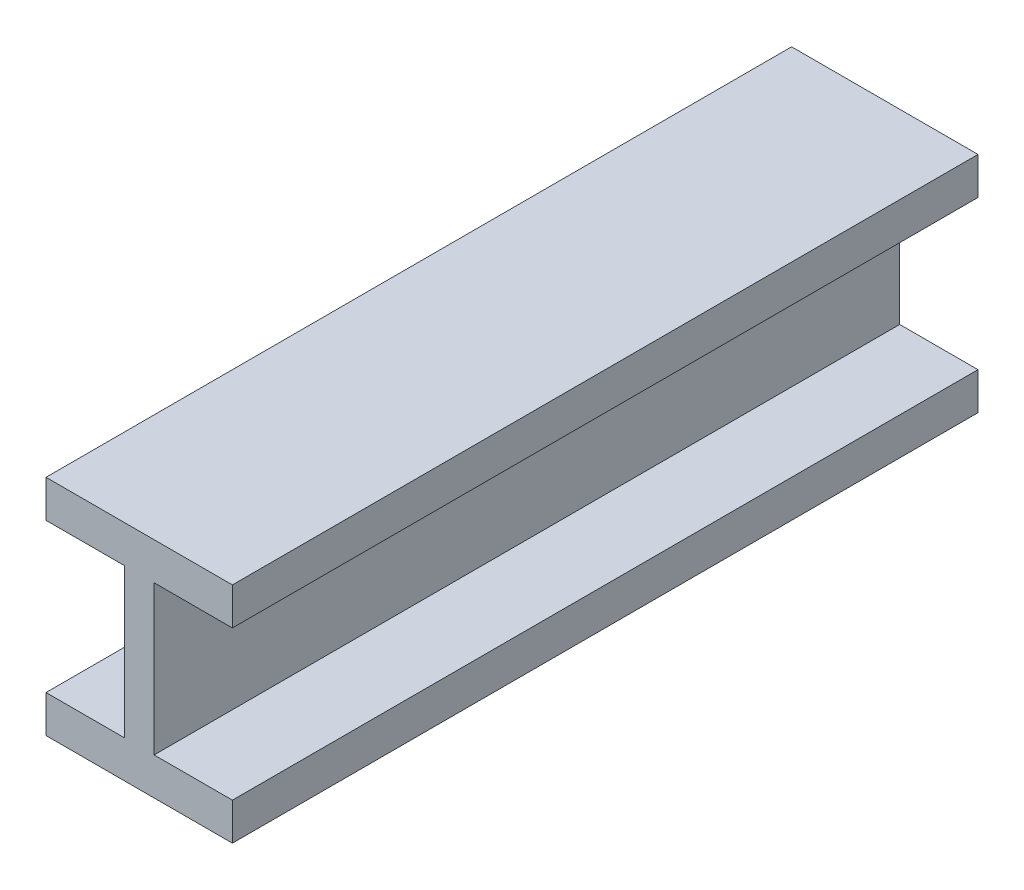
SolidWorks part; units mm, degrees
material "ABS P430"
ref_plane "Front Plane" through (0, 0, 0) normal (0, 0, 1) x (1, 0, 0)
ref_plane "Top Plane" through (0, 0, 0) normal (0, 1, 0) x (1, 0, 0)
ref_plane "Right Plane" through (0, 0, 0) normal (1, 0, 0) x (0, 0, -1)
sketch "Sketch3" plane through (0, 0, 0) normal (0, 1, 0) x (1, 0, 0)
  line L0 (0, 0) -> (0, 100.0652)
  point P3 (0, 50.0326)
  dimension "D1" = 100.0652
sketch "Sketch1" plane through (0, 0, 0) normal (0, 0, 1) x (1, 0, 0)
  line L1 (-12.5, -15) -> (12.5, -15)
  line L2 (-12.5, -15) -> (-12.5, 15)
  line L3 (-12.5, 15) -> (12.5, 15)
  line L4 (12.5, -15) -> (12.5, 15)
  line L5 (-12.5, -15) -> (12.5, 15) construction
  line L6 (-12.5, 15) -> (12.5, -15) construction
  line L7 (-12.5, -10) -> (12.5, -10)
  line L8 (-2, -10) -> (-2, 10)
  line L9 (-12.5, 10) -> (12.5, 10)
  line L10 (2, -10) -> (2, 10)
  line L11 (-2, -10) -> (2, 10) construction
  line L12 (-2, 10) -> (2, -10) construction
  point P0 (0, 0)
  point P6 (0, 0)
  dimension "D1" = 5
  dimension "D2" = 5
  dimension "D3" = 4
  dimension "D4" = 25
  dimension "D5" = 20
extrude "Boss-Extrude1" add sketch "Sketch1" against normal blind 100 contours L2 L9 L4 L3 | L7 L10 L9 L8 | L7 L2 L1 L4 region at (0, -12.5, 0) region at (0, 12.5, 0) region at (0, 0, 0)
ref_point "Point1" [suppressed]
equation "\"a\" = 25"
equation "\"b\"= 5"
equation "\"c\" = 20"
equation "\"d\" = 4"
equation "\"D1@Sketch1\"=\"b\""
equation "\"D2@Sketch1\"=\"b\""
equation "\"D5@Sketch1\"=\"c\""
equation "\"D3@Sketch1\"=\"d\""
equation "\"D4@Sketch1\"=\"a\""
equation "\"load\"= 20"
